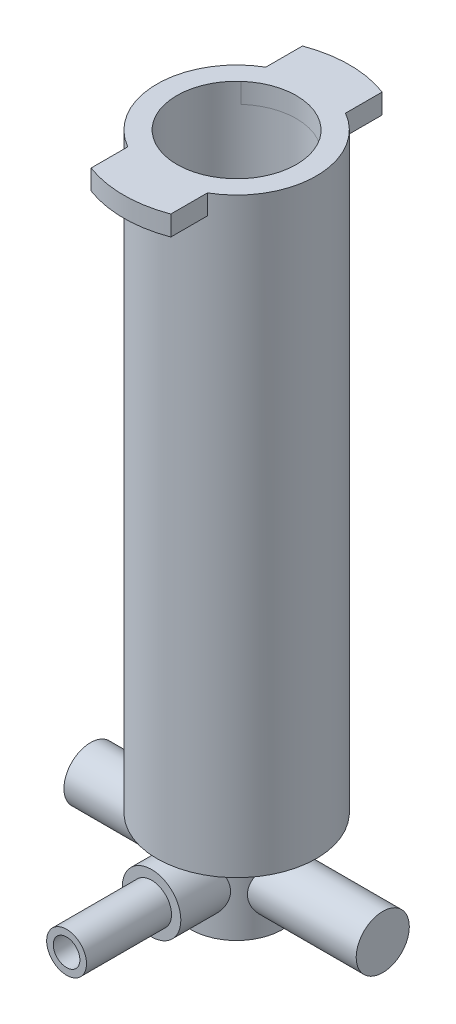
SolidWorks part; units mm, degrees
ref_plane "Front Plane" through (0, 0, 0) normal (0, 0, 1) x (1, 0, 0)
ref_plane "Top Plane" through (0, 0, 0) normal (0, 1, 0) x (1, 0, 0)
ref_plane "Right Plane" through (0, 0, 0) normal (1, 0, 0) x (0, 0, -1)
sketch "Sketch1" plane through (0, 0, 0) normal (0, 1, 0) x (1, 0, 0)
  circle A0 centre (0, 0) radius 6
extrude "Boss-Extrude1" add sketch "Sketch1" along normal blind 44.5
shell "Shell1" thickness 1.5 removed face at (0, 44.5, 6)
sketch "Sketch3" plane through (0, 0, 0) normal (0, -1, 0) x (1, 0, 0)
  circle A0 centre (0, 0) radius 3.45
extrude "Boss-Extrude3" add sketch "Sketch3" along normal blind 5.9
shell "Shell2" thickness 1.5 removed face at (0, 1.5, 4.5)
sketch "Sketch5" plane through (0, 0, 0) normal (0, 0, 1) x (1, 0, 0)
  line L0 (0, -5.9) -> (0, 0) construction
  circle A0 centre (0, -2.7032) radius 2.2
extrude "Boss-Extrude4" add sketch "Sketch5" along normal blind 6.4
sketch "Sketch6" plane through (0, 0, 6.4) normal (0, 0, 1) x (1, 0, 0)
  circle A0 centre (0, -2.7032) radius 1.5
extrude "Boss-Extrude5" add sketch "Sketch6" along normal blind 6.4
sketch "Sketch7" plane through (0, 0, 12.8) normal (0, 0, 1) x (1, 0, 0)
  circle A0 centre (0, -2.7032) radius 1
extrude "Cut-Extrude1" cut sketch "Sketch7" against normal blind 12.4
sketch "Sketch8" plane through (0, -4.4, 0) normal (0, 1, 0) x (1, 0, 0)
  circle A0 centre (0, 0) radius 1.95
extrude "Cut-Extrude2" cut sketch "Sketch8" along normal through all
sketch "Sketch9" plane through (0, 0, 0) normal (1, 0, 0) x (0, 0, -1)
  line L0 (0, 0) -> (0, -5.869) construction
  circle A0 centre (0, -2.9345) radius 2
extrude "Boss-Extrude6" add sketch "Sketch9" along normal blind 11
sketch "Sketch10" plane through (0, -4.4, 0) normal (0, 1, 0) x (1, 0, 0)
  line L0 (0, 1.95) -> (0, -2) construction
  circle A0 centre (0, -0.025) radius 1.975
extrude "Cut-Extrude3" cut sketch "Sketch10" along normal through all contours A0
sketch "Sketch11" plane through (0, 0, 12.8) normal (0, 0, 1) x (1, 0, 0)
  circle A0 centre (0, -2.7032) radius 1
extrude "Cut-Extrude4" cut sketch "Sketch11" against normal blind 12
mirror "Mirror5" about plane through (0, 0, 0) normal (1, 0, 0) of bodies 111
sketch "Sketch14" plane through (0, 44.5, 0) normal (0, 1, 0) x (1, 0, 0)
  line L1 (-3, -3.3463) -> (-3, -7.953)
  line L3 (3, -3.3463) -> (3, -7.953)
  line L4 (-0.9935, 0) -> (-0.4747, 0) construction
  line L5 (3, 3.3463) -> (3, 7.953)
  line L6 (-3, 3.3463) -> (-3, 7.953)
  arc A0 (-3, -7.953) -> (3, -7.953) centre (0, 0) ccw
  arc A1 (3, -3.3463) -> (-3, -3.3463) centre (0, 0) cw
  arc A2 (-3, 7.953) -> (3, 7.953) centre (0, 0) cw
  arc A3 (3, 3.3463) -> (-3, 3.3463) centre (0, 0) ccw
extrude "Boss-Extrude9" add sketch "Sketch14" against normal blind 1.5
